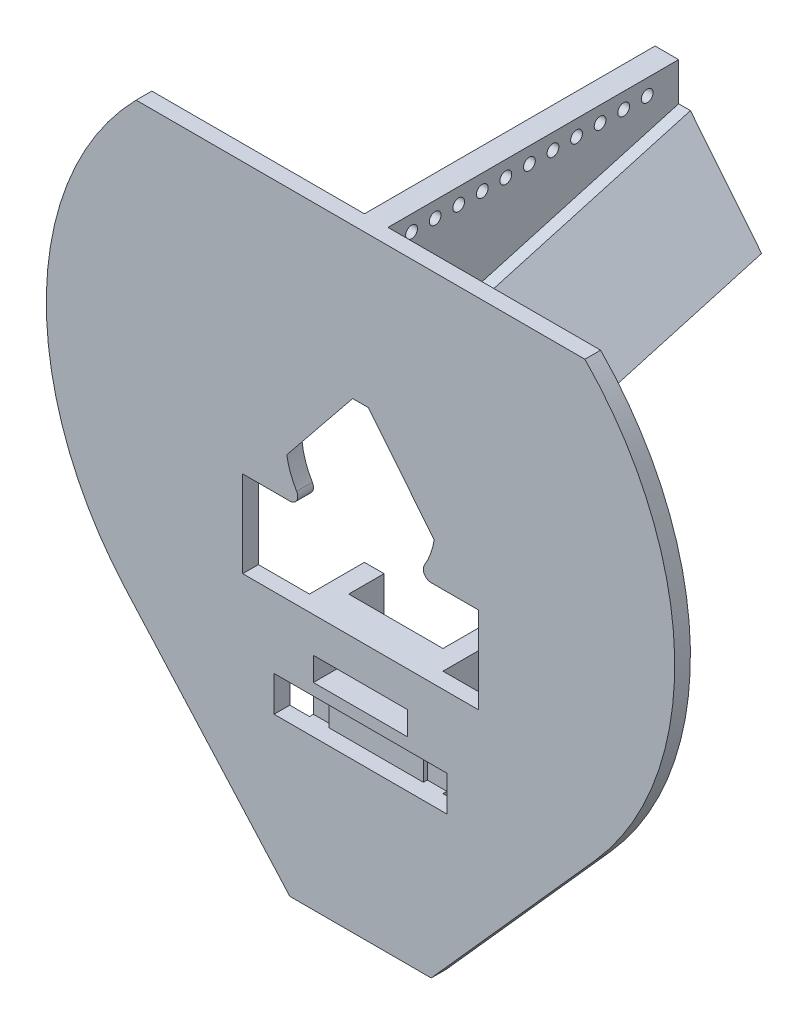
SolidWorks part; units mm, degrees
ref_plane "Front Plane" through (0, 0, 0) normal (0, 0, 1) x (1, 0, 0)
ref_plane "Top Plane" through (0, 0, 0) normal (0, 1, 0) x (1, 0, 0)
ref_plane "Right Plane" through (0, 0, 0) normal (1, 0, 0) x (0, 0, -1)
sketch "Sketch1" plane through (0, 0, 0) normal (0, 0, 1) x (1, 0, 0)
  line L0 (0, 0) -> (0, 70.7304) construction
  line L1 (0, 0) -> (0, -66.9614) construction
  line L2 (7, -6.4226) -> (15, -6.4226)
  line L3 (15, -6.4226) -> (15, -17.4226)
  line L4 (15, -17.4226) -> (-15, -17.4226)
  line L5 (-7, -6.4226) -> (-15, -6.4226)
  line L6 (-15, -6.4226) -> (-15, -17.4226)
  line L7 (-28.5657, 28) -> (28.5657, 28)
  line L8 (-29.8496, -26.6271) -> (-9, -50)
  line L9 (-9, -50) -> (9, -50)
  line L10 (29.8496, -26.6271) -> (9, -50)
  arc A0 (7, -6.4226) -> (-7, -6.4226) centre (0, 0) ccw
  arc A1 (-28.5657, 28) -> (-29.8496, -26.6271) centre (0, 0) ccw
  arc A2 (29.8496, -26.6271) -> (28.5657, 28) centre (0, 0) ccw
  point P12 (0, -17.4226)
  point P17 (0, -50)
  dimension "D1" = 19
  dimension "D5" = 80
  dimension "D2" = 11
  dimension "D3" = 7
  dimension "D4" = 15
  dimension "D6" = 28
  dimension "D7" = 50
  dimension "D8" = 9
extrude "Boss-Extrude1" add sketch "Sketch1" along normal blind 2
sketch "Sketch2" plane through (0, 0, 0) normal (1, 0, 0) x (0, 0, -1)
  line L0 (0, 9.5) -> (37, 20)
  line L1 (0, -26.6271) -> (0, 28) construction
  line L2 (37, 20) -> (37, 28)
  line L3 (37, 28) -> (0, 28)
  line L4 (0, 28) -> (0, 9.5)
  circle A0 centre (3, 26) radius 0.75
  circle A1 centre (6, 26) radius 0.75
  circle A2 centre (9, 26) radius 0.75
  circle A3 centre (12, 26) radius 0.75
  circle A4 centre (15, 26) radius 0.75
  circle A5 centre (18, 26) radius 0.75
  circle A6 centre (21, 26) radius 0.75
  circle A7 centre (24, 26) radius 0.75
  circle A8 centre (27, 26) radius 0.75
  circle A9 centre (30, 26) radius 0.75
  circle A10 centre (33, 26) radius 0.75
  dimension "D3" = 1.5
  dimension "D1" = 8
  dimension "D2" = 37
  dimension "D4" = 2
  dimension "D5" = 3
  dimension "D6" = 11
extrude "Boss-Extrude2" add sketch "Sketch2" along normal mid plane 3
ref_plane "Plane1" through (0, 0.708, -2.495) normal (0, -0.273, 0.962) x (1, 0, 0)
sketch "Sketch3" plane through (0, 0.708, -2.495) normal (0, -0.273, 0.962) x (1, 0, 0)
  line L0 (1, 9.0884) -> (-1, 9.0884)
  line L1 (-1, 9.0884) -> (-9.3805, -0.8991)
  line L2 (-9.3805, -0.8991) -> (-12.0616, 1.3506)
  line L3 (-12.0616, 1.3506) -> (-3, 12.1499)
  line L4 (-3, 12.1499) -> (3, 12.1499)
  line L5 (0, 7.2017) -> (0, 17.4273) construction
  line L6 (12.0616, 1.3506) -> (3, 12.1499)
  line L7 (9.3805, -0.8991) -> (12.0616, 1.3506)
  line L8 (1, 9.0884) -> (9.3805, -0.8991)
  ellipse E0 centre (0, 0) end of major axis (9.5, 0) minor radius 9.1391 (0, 9.1391) -> (-7, -6.1786) ccw construction
  ellipse E1 centre (0, 0.546) end of major axis (9.5, 0.546) minor radius 9.1391 (7, -5.6326) -> (-7, -5.6326) ccw construction
  point P17 (0, 12.1499)
  dimension "D1" = 2
  dimension "D2" = 3.5
  dimension "D3" = 3
  dimension "D4" = 40
extrude "Boss-Extrude3" add sketch "Sketch3" against normal up to surface and the other way up to surface up to face at (0, 24, -37) other way up to face at (0, -16.1246, 2)
sketch "Sketch4" plane through (0, 0, 0) normal (1, 0, 0) x (0, 0, -1)
  line L0 (20.3765, 1.7087) -> (25.2343, 8.5651)
  line L1 (37, 11.904) -> (0, 1.404) construction
  line L2 (25.2343, 8.5651) -> (31.1444, 4.3777)
  line L3 (31.1444, 4.3777) -> (20.3765, 1.7087)
extrude "Cut-Extrude1" cut sketch "Sketch4" against normal mid plane 33
sketch "Sketch5" plane through (0, 0, 0) normal (0, 0, -1) x (-1, 0, 0)
  line L0 (0, 0) -> (0, -55.4297) construction
  line L1 (15, -17.4226) -> (-15, -17.4226) construction
  line L2 (-8.5, -17.4226) -> (-6, -17.4226)
  line L3 (-8.5, -17.4226) -> (-8.5, -39.4226)
  line L4 (-8.5, -39.4226) -> (-6, -39.4226)
  line L5 (-6, -17.4226) -> (-6, -39.4226)
  line L6 (6, -17.4226) -> (6, -39.4226)
  line L7 (8.5, -39.4226) -> (6, -39.4226)
  line L8 (8.5, -17.4226) -> (8.5, -39.4226)
  line L9 (8.5, -17.4226) -> (6, -17.4226)
  dimension "D1" = 22
  dimension "D2" = 2.5
  dimension "D3" = 6
extrude "Boss-Extrude4" add sketch "Sketch5" along normal blind 7
sketch "Sketch6" plane through (0, 0, 2) normal (0, 0, 1) x (1, 0, 0)
  line L0 (0, 0) -> (0, -53.715) construction
  line L1 (-15, -17.4226) -> (15, -17.4226) construction
  line L2 (-6, -21.9226) -> (6, -21.9226)
  line L3 (-11, -26.4226) -> (-11, -30.9226)
  line L4 (-6, -24.9226) -> (6, -24.9226)
  line L5 (6, -21.9226) -> (6, -24.9226)
  line L6 (-11, -26.4226) -> (11, -26.4226)
  line L7 (-6, -21.9226) -> (-6, -24.9226)
  line L8 (-11, -30.9226) -> (11, -30.9226)
  line L9 (11, -26.4226) -> (11, -30.9226)
  point P5 (0, -21.9226)
  point P9 (0, -26.4226)
  point P15 (0, -30.9226)
  point P17 (0, -24.9226)
  dimension "D1" = 11
  dimension "D2" = 9
  dimension "D3" = 4.5
  dimension "D4" = 4.5
  dimension "D5" = 3
  dimension "D6" = 12
extrude "Cut-Extrude2" cut sketch "Sketch6" against normal blind 2.5
sketch "Sketch7" plane through (0, 0, 0) normal (0, 0, -1) x (-1, 0, 0)
  line L0 (6, -17.4226) -> (6, -39.4226) construction
  line L1 (-6, -24.9226) -> (6, -24.9226)
  line L2 (-6, -24.9226) -> (-6, -31.9226)
  line L3 (-6, -31.9226) -> (6, -31.9226)
  line L4 (6, -24.9226) -> (6, -31.9226)
  line L7 (-6, -17.4226) -> (6, -17.4226)
  line L8 (-6, -17.4226) -> (-6, -21.9226)
  line L9 (-6, -21.9226) -> (6, -21.9226)
  line L10 (6, -17.4226) -> (6, -21.9226)
  dimension "D1" = 7
extrude "Boss-Extrude5" add sketch "Sketch7" along normal blind 2.5
fillet "Fillet1" radius 4 1 edges at (0, -31.9226, 0)
fillet "Fillet2" radius 1 2 edges at (-7, -6.4226, 1) (7, -6.4226, 1)
sketch "Sketch8" plane through (0, 0.708, -2.495) normal (0, -0.273, 0.962) x (1, 0, 0)
  line L0 (-9.3805, -0.8991) -> (-1, 9.0884) construction
  line L1 (1, 9.0884) -> (9.3805, -0.8991) construction
  circle A0 centre (0, 0.9458) radius 6
  circle A1 centre (0, 4.135) radius 3.95
  dimension "D1" = 12
  dimension "D2" = 7.9
